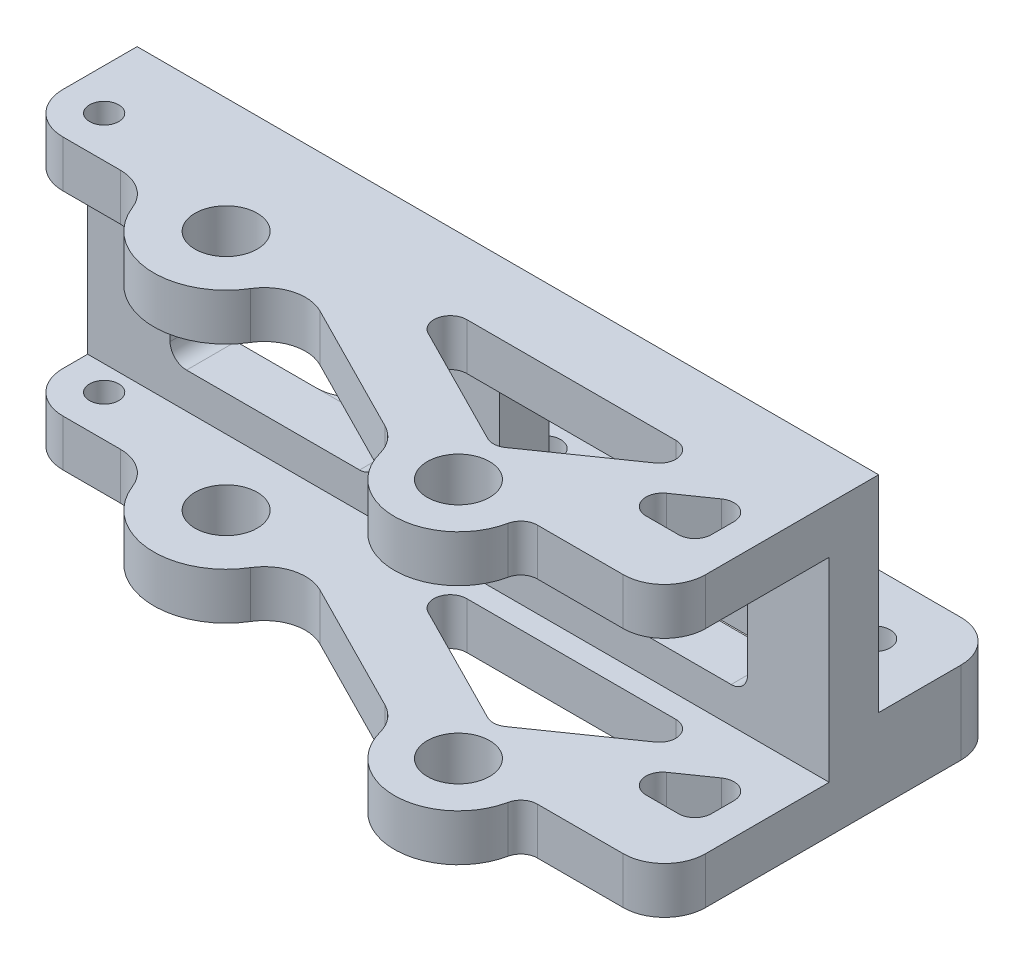
SolidWorks part; units mm, degrees
ref_plane "Front Plane" through (0, 0, 0) normal (0, 0, 1) x (1, 0, 0)
ref_plane "Top Plane" through (0, 0, 0) normal (0, 1, 0) x (1, 0, 0)
ref_plane "Right Plane" through (0, 0, 0) normal (1, 0, 0) x (0, 0, -1)
sketch "Sketch1" plane through (0, 0, 0) normal (0, 0, 1) x (1, 0, 0)
  line L1 (57.15, -22.225) -> (-57.15, -22.225)
  line L2 (57.15, -22.225) -> (57.15, 22.225)
  line L3 (57.15, 22.225) -> (-57.15, 22.225)
  line L4 (-57.15, -22.225) -> (-57.15, 22.225)
  line L5 (57.15, -22.225) -> (-57.15, 22.225) construction
  line L6 (57.15, 22.225) -> (-57.15, -22.225) construction
  point P0 (0, 0)
  dimension "D1" = 44.45
  dimension "D2" = 114.3
extrude "Boss-Extrude1" add sketch "Sketch1" along normal blind 64.77
sketch "Sketch2" plane through (0, 0, 64.77) normal (0, 0, 1) x (1, 0, 0)
  line L0 (-57.15, 22.225) -> (-57.15, -22.225) construction
  line L1 (57.15, -15.025) -> (-57.15, -15.025)
  line L2 (57.15, -15.025) -> (57.15, 15.025)
  line L3 (57.15, 15.025) -> (-57.15, 15.025)
  line L4 (-57.15, -15.025) -> (-57.15, 15.025)
  line L5 (57.15, -15.025) -> (-57.15, 15.025) construction
  line L6 (57.15, 15.025) -> (-57.15, -15.025) construction
  line L7 (57.15, 22.225) -> (-57.15, 22.225) construction
  point P0 (0, 0)
  dimension "D1" = 7.2
extrude "Cut-Extrude2" cut sketch "Sketch2" against normal blind 35.56
sketch "Sketch3" plane through (0, 0, 0) normal (0, 0, -1) x (-1, 0, 0)
  line L0 (-57.15, -22.225) -> (-57.15, 22.225) construction
  line L1 (57.15, 22.225) -> (-57.15, 22.225)
  line L2 (57.15, 22.225) -> (57.15, -9.525)
  line L3 (57.15, -9.525) -> (-57.15, -9.525)
  line L4 (-57.15, 22.225) -> (-57.15, -9.525)
  line L5 (57.15, -22.225) -> (-57.15, -22.225) construction
  dimension "D1" = 12.7
extrude "Cut-Extrude3" cut sketch "Sketch3" against normal blind 21.59
sketch "Sketch5" plane through (0, -22.225, 0) normal (0, -1, 0) x (1, 0, 0)
  line L0 (-3.81, 12.06) -> (46.99, 12.06) construction
  line L1 (57.15, 21.59) -> (-57.15, 21.59) construction
  line L2 (57.15, 64.77) -> (57.15, 0) construction
  circle A0 centre (-3.81, 12.06) radius 2.415
  circle A1 centre (46.99, 12.06) radius 2.415
  dimension "D3" = 4.83
  dimension "D4" = 10.16
  dimension "D1" = 9.53
  dimension "D2" = 50.8
extrude "Cut-Extrude4" cut sketch "Sketch5" against normal blind 25.4
sketch "Sketch7" plane through (0, -22.225, 0) normal (0, -1, 0) x (1, 0, 0)
  line L0 (57.15, 64.77) -> (57.15, 0) construction
  line L1 (-57.15, 0) -> (57.15, 0) construction
  circle A0 centre (25.4, 54.61) radius 4.8
  circle A1 centre (-25.65, 39.37) radius 4.8
  dimension "D1" = 9.6
  dimension "D2" = 31.75
  dimension "D3" = 39.37
  dimension "D4" = 9.6
  dimension "D5" = 51.05
  dimension "D6" = 15.24
extrude "Cut-Extrude6" cut sketch "Sketch7" against normal up to surface (44.45 mm away) up to face at (0, 22.225, 43.18)
sketch "Sketch9" plane through (0, 0, 29.21) normal (0, 0, 1) x (1, 0, 0)
  line L5 (57.15, 15.025) -> (-57.15, 15.025) construction
  line L6 (-44.45, 15.025) -> (-12.7, 15.025)
  line L7 (-44.45, 15.025) -> (-44.45, -15.025)
  line L8 (-44.45, -15.025) -> (-12.7, -15.025)
  line L9 (-12.7, 15.025) -> (-12.7, -15.025)
  line L10 (-57.15, -15.025) -> (57.15, -15.025) construction
  line L11 (-57.15, 15.025) -> (-57.15, -15.025) construction
  line L12 (57.15, -15.025) -> (57.15, 15.025) construction
  dimension "D1" = 69.85
  dimension "25in" = 12.7
extrude "Cut-Extrude7" cut sketch "Sketch9" against normal through all both and the other way through all
sketch "Sketch16" plane through (0, -22.225, 0) normal (0, -1, 0) x (1, 0, 0)
  line L1 (-44.45, 29.21) -> (-57.15, 29.21) construction
  line L4 (-36.8, 39.37) -> (-36.8, 29.21)
  line L8 (-57.15, 64.77) -> (57.15, 64.77)
  line L9 (57.15, 64.77) -> (57.15, 54.61)
  line L10 (57.15, 64.77) -> (57.15, 0) construction
  line L11 (-14.5, 39.37) -> (15.52, 54.61)
  line L12 (35.28, 54.61) -> (57.15, 54.61)
  line L13 (-49.091, 29.21) -> (-57.15, 29.21)
  line L14 (-36.8, 29.21) -> (-49.091, 29.21)
  line L15 (-57.15, 29.21) -> (-57.15, 64.77)
  arc A2 (35.28, 54.61) -> (15.52, 54.61) centre (25.4, 54.61) ccw
  arc A3 (-14.5, 39.37) -> (-36.8, 39.37) centre (-25.65, 39.37) ccw
  circle A4 centre (-25.65, 39.37) radius 4.8 construction
  circle A5 centre (25.4, 54.61) radius 4.8 construction
  dimension "D1" = 6.35
  dimension "D2" = 5.08
  dimension "D3" = 10.16
extrude "Cut-Extrude8" cut sketch "Sketch16" against normal through all
sketch "Sketch14" plane through (-12.7, 0, 0) normal (-1, 0, 0) x (0, 0, 1)
  line L0 (0, -15.025) -> (29.21, -15.025) construction
  line L1 (21.59, -9.525) -> (0, -9.525)
  line L2 (21.59, -9.525) -> (21.59, -15.025)
  line L3 (21.59, -15.025) -> (0, -15.025)
  line L4 (0, -9.525) -> (0, -15.025)
extrude "Boss-Extrude2" add sketch "Sketch14" along normal up to next
sketch "Sketch17" plane through (0, 0, 21.59) normal (0, 0, 1) x (1, 0, 0)
  line L1 (-12.7, -15.025) -> (-44.45, -15.025)
  line L2 (-12.7, -15.025) -> (-12.7, -9.525)
  line L3 (-12.7, -9.525) -> (-44.45, -9.525)
  line L4 (-44.45, -15.025) -> (-44.45, -9.525)
extrude "Boss-Extrude3" add sketch "Sketch17" along normal up to surface (7.62 mm away) up to face at (22.225, 0, 29.21)
sketch "Sketch25" plane through (-36.8, 0, 0) normal (-1, 0, 0) x (0, 0, 1)
  line L0 (39.37, 15.025) -> (29.21, 15.025) construction
  line L1 (29.21, 22.225) -> (39.37, 22.225)
  line L2 (29.21, 22.225) -> (29.21, 15.025)
  line L3 (29.21, 15.025) -> (39.37, 15.025)
  line L4 (39.37, 22.225) -> (39.37, 15.025)
  line L5 (39.37, -22.225) -> (50.52, -22.225) construction
  line L6 (29.21, -15.025) -> (39.37, -15.025)
  line L7 (29.21, -15.025) -> (29.21, -22.225)
  line L8 (29.21, -22.225) -> (39.37, -22.225)
  line L9 (39.37, -15.025) -> (39.37, -22.225)
  dimension "D1" = 10.16
extrude "Boss-Extrude5" add sketch "Sketch25" along normal up to surface (20.35 mm away) up to face at (-57.15, -3.175, 16.9333)
sketch "Sketch28" plane through (0, -22.225, 0) normal (0, -1, 0) x (-1, 0, 0)
sketch "Sketch30" plane through (0, -22.225, 0) normal (0, -1, 0) x (-1, 0, 0)
  line L2 (57.15, -39.37) -> (36.8, -39.37) construction
  line L4 (57.15, -39.37) -> (57.15, 0) construction
  point P10 (50.8, -33.02)
  dimension "D1" = 6.35
  dimension "D2" = 6.35
hole_wizard "#8 Clearance Hole1" positions "Sketch30" profile "Sketch29" hole size "#8" standard "ANSI Inch" end condition through all
sketch "Sketch29" plane through (-50.8, -22.225, 33.02) normal (1, 0, 0) x (0, 0, -1)
  line L0 (0, 0) -> (0, 44.45)
  line L1 (0, 44.45) -> (2.2479, 44.45)
  line L2 (2.2479, 44.45) -> (2.2479, 0)
  line L5 (2.2479, 0) -> (0, 0)
  line L11 (0, -6.35) -> (0, 107.95) construction
  dimension "Thru Hole Dia." = 4.4958
  dimension "Thru Hole Depth" = 44.45
sketch "Sketch31" plane through (0, 0, 0) normal (0, 0, -1) x (-1, 0, 0)
  line L1 (-57.15, -9.525) -> (57.15, -9.525)
  line L2 (-57.15, -9.525) -> (-57.15, -22.225)
  line L3 (-57.15, -22.225) -> (57.15, -22.225)
  line L4 (57.15, -9.525) -> (57.15, -22.225)
extrude "Cut-Extrude9" cut sketch "Sketch31" against normal blind 2.54
sketch "Sketch32" plane through (0, -22.225, 0) normal (0, -1, 0) x (1, 0, 0)
  line L0 (-5.9182, 32.621) -> (23.5316, 47.5715)
  line L1 (23.5316, 47.5715) -> (45.0021, 32.621)
  line L2 (45.0021, 32.621) -> (-5.9182, 32.621)
  line L3 (-14.5, 39.37) -> (15.52, 54.61) construction
  line L4 (36.6419, 45.0215) -> (52.2621, 45.0215)
  line L5 (52.2621, 45.0215) -> (52.2621, 34.1447)
  line L6 (52.2621, 34.1447) -> (36.6419, 45.0215)
  line L7 (57.15, 2.54) -> (-57.15, 2.54) construction
  line L8 (-57.15, 2.54) -> (-7.2674, 2.54)
  line L9 (-57.15, 2.54) -> (-57.15, 21.59)
  line L10 (-57.15, 21.59) -> (-26.9888, 21.59)
  line L11 (-7.2674, 2.54) -> (-26.9888, 21.59)
  line L12 (-57.15, 39.37) -> (-57.15, 2.54) construction
  line L16 (-44.45, 21.59) -> (-57.15, 21.59) construction
  dimension "D1" = 30.1612
extrude "Cut-Extrude10" cut sketch "Sketch32" against normal through all
fillet "Fillet2" radius 2.54 2 edges at (35.28, 18.625, 54.61) (35.28, -18.625, 54.61)
fillet "Fillet3" radius 6.35 13 edges at (57.15, -15.875, 2.54) (57.15, 18.625, 54.61) (57.15, -18.625, 54.61) (15.52, -18.625, 54.61) (15.52, 18.625, 54.61) (-14.5, 18.625, 39.37) (-14.5, -18.625, 39.37) (-7.2674, -15.875, 2.54) (-26.9888, -15.875, 21.59) (-57.15, -18.625, 39.37) (-57.15, 18.625, 39.37) (-36.8, 18.625, 39.37) (-36.8, -18.625, 39.37)
sketch "Sketch33" plane through (0, -9.525, 0) normal (0, 1, 0) x (1, 0, 0)
  line L1 (57.15, -21.59) -> (-40.8747, -21.59)
  line L2 (57.15, -21.59) -> (57.15, 0)
  line L3 (57.15, 0) -> (-40.8747, 0)
  line L4 (-40.8747, -21.59) -> (-40.8747, 0)
split line "Split Line1"
sketch "Sketch35" plane through (0, -22.225, 0) normal (0, -1, 0) x (1, 0, 0)
  line L0 (-4.4635, 21.59) -> (47.1888, 21.59)
  line L1 (47.1888, 21.59) -> (34.29, 8.6912)
  line L2 (34.29, 8.6912) -> (8.89, 8.6912)
  line L3 (8.89, 8.6912) -> (-4.4635, 21.59)
  line L4 (-9.113, 4.3228) -> (-25.1431, 19.8072) construction
  line L5 (-4.7013, 2.54) -> (50.8, 2.54) construction
  line L6 (-29.5549, 21.59) -> (-12.7, 21.59) construction
  line L7 (-3.81, 12.06) -> (46.99, 12.06) construction
  point P14 (21.59, 12.06)
  point P15 (21.59, 8.6912)
  dimension "D1" = 225
  dimension "D2" = 25.4
extrude "Cut-Extrude11" cut sketch "Sketch35" against normal through all
sketch "Sketch36" plane through (0, 0, 29.21) normal (0, 0, 1) x (1, 0, 0)
  line L0 (12.5906, 15.025) -> (-7.8042, 15.025) construction
  line L1 (6.35, 15.025) -> (44.575, 15.025)
  line L2 (6.35, 15.025) -> (6.35, -9.525)
  line L3 (6.35, -9.525) -> (44.575, -9.525)
  line L4 (44.575, 15.025) -> (44.575, -9.525)
  line L5 (-12.7, -9.525) -> (-12.7, 15.025) construction
  dimension ".5" = 19.05
extrude "Cut-Extrude12" cut sketch "Sketch36" against normal through all
fillet "Fillet1" radius 2.54 16 edges at (-5.9182, 18.625, 32.621) (45.0021, 18.625, 32.621) (23.5316, 18.625, 47.5715) (36.6419, 18.625, 45.0215) (52.2621, 18.625, 45.0215) (52.2621, 18.625, 34.1447) (52.2621, -18.625, 45.0215) (52.2621, -18.625, 34.1447) (36.6419, -18.625, 45.0215) (45.0021, -18.625, 32.621) (23.5316, -18.625, 47.5715) (-5.9182, -18.625, 32.621) (47.1888, -15.875, 21.59) (34.29, -15.875, 8.6912) (8.89, -15.875, 8.6912) (-4.4635, -15.875, 21.59)
sketch "Sketch34" plane through (0, 0, 21.59) normal (0, 0, -1) x (-1, 0, 0)
  line L0 (57.15, -22.225) -> (57.15, 22.225) construction
  line L1 (-57.15, -9.525) -> (57.15, -9.525)
  line L2 (-57.15, -9.525) -> (-57.15, 9.525)
  line L3 (-57.15, 9.525) -> (57.15, 9.525)
  line L4 (57.15, -9.525) -> (57.15, 9.525)
  dimension "D1" = 19.05
split line "Split Line2"
fillet "Fillet4" radius 2.54 8 edges at (44.575, 15.025, 25.4) (6.35, 15.025, 25.4) (-12.7, 15.025, 25.4) (-44.45, 15.025, 25.4) (-44.45, -9.525, 25.4) (-12.7, -9.525, 25.4) (6.35, -9.525, 25.4) (44.575, -9.525, 25.4)
